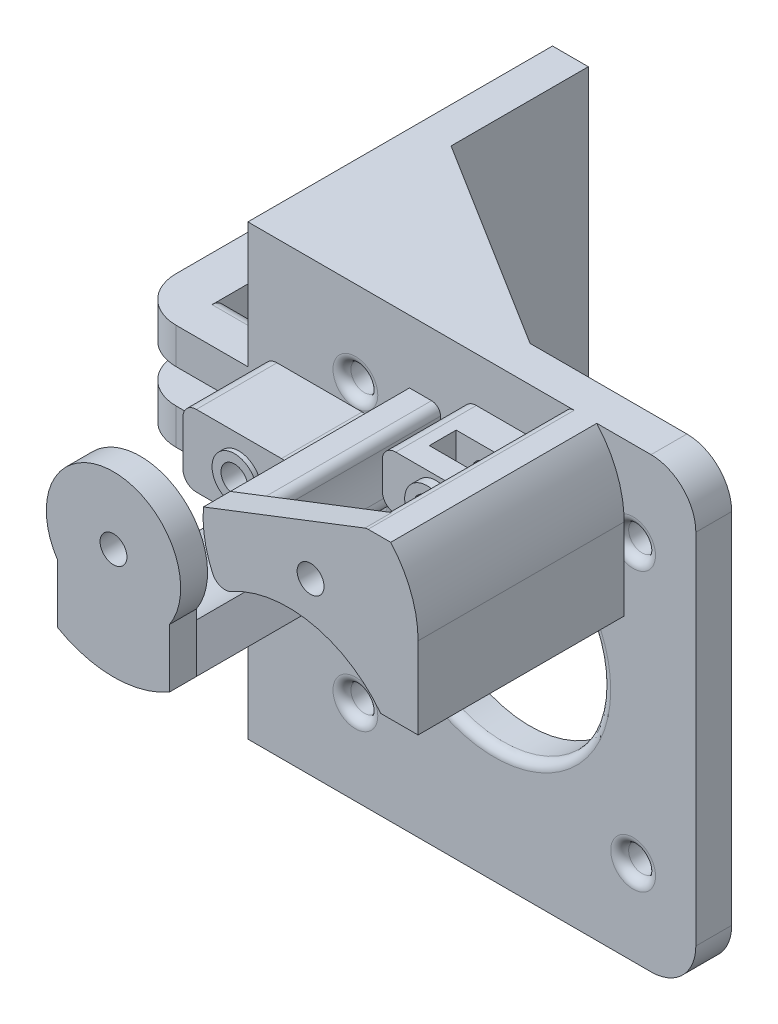
SolidWorks part; units mm, degrees
ref_plane "Plano frontal" through (0, 0, 0) normal (0, 0, 1) x (1, 0, 0)
ref_plane "Plano superior" through (0, 0, 0) normal (0, 1, 0) x (1, 0, 0)
ref_plane "Plano direito" through (0, 0, 0) normal (1, 0, 0) x (0, 0, -1)
sketch "Esboço1" plane through (0, 0, 0) normal (0, 0, 1) x (1, 0, 0)
  line L0 (-22.5, 25) -> (-27.5, 25)
  line L1 (-22.5, 25) -> (22.5, 25)
  line L2 (-22.5, 25) -> (-22.5, -25) construction
  line L3 (-22.5, -25) -> (22.5, -25)
  line L4 (22.5, 25) -> (22.5, -25)
  line L5 (-22.5, 25) -> (22.5, -25) construction
  line L6 (-22.5, -25) -> (22.5, 25) construction
  line L7 (15.5, -15.5) -> (-15.5, -15.5) construction
  line L8 (15.5, -15.5) -> (15.5, 15.5) construction
  line L9 (15.5, 15.5) -> (-15.5, 15.5) construction
  line L10 (-15.5, -15.5) -> (-15.5, 15.5) construction
  line L11 (15.5, -15.5) -> (-15.5, 15.5) construction
  line L12 (15.5, 15.5) -> (-15.5, -15.5) construction
  line L13 (-27.5, 25) -> (-27.5, -25)
  line L14 (-27.5, -25) -> (-22.5, -25)
  circle A0 centre (-15.5, 15.5) radius 1.5
  circle A1 centre (-15.5, -15.5) radius 1.5
  circle A2 centre (15.5, -15.5) radius 1.5
  circle A3 centre (15.5, 15.5) radius 1.5
  circle A4 centre (0, 0) radius 12
  point P0 (0, 0)
  point P6 (0, 0)
  dimension "D2" = 3
  dimension "D5" = 24
  dimension "D1" = 31
  dimension "D3" = 45
  dimension "D4" = 50
  dimension "D6" = 5
extrude "Ressalto-extrusão1" add sketch "Esboço1" along normal blind 4
sketch "Esboço2" plane through (0, 0, 0) normal (0, 0, -1) x (-1, 0, 0)
  line L0 (27.5, 25) -> (27.5, -25) construction
  line L1 (27.5, 25) -> (23.5, 25)
  line L2 (27.5, 25) -> (27.5, -25)
  line L3 (27.5, -25) -> (23.5, -25)
  line L4 (23.5, 25) -> (23.5, -25)
  line L5 (-22.5, 25) -> (27.5, 25) construction
  line L6 (27.5, -25) -> (-22.5, -25) construction
  dimension "D1" = 4
extrude "Ressalto-extrusão2" add sketch "Esboço2" along normal blind 30
sketch "Esboço3" plane through (0, 0, 0) normal (0, 0, -1) x (-1, 0, 0)
  line L0 (0, 0) -> (23.5, 0) construction
  line L1 (23.5, 25) -> (0, 25)
  line L2 (23.5, 25) -> (23.5, 22)
  line L3 (23.5, 22) -> (0, 22)
  line L4 (0, 25) -> (0, 22)
  line L5 (23.5, 25) -> (23.5, -25) construction
  line L6 (0, -25) -> (0, -22)
  line L7 (23.5, -22) -> (0, -22)
  line L8 (23.5, -25) -> (23.5, -22)
  line L9 (23.5, -25) -> (0, -25)
  dimension "D1" = 3
extrude "Ressalto-extrusão3" add sketch "Esboço3" along normal blind 15
chamfer "Chanfro1" distance 15 angle 58 2 edges at (0, -23.5, -15) (0, 23.5, -15) first distance on face at (0, -23.5, -7.5) first distance on face at (0, 23.5, -7.5)
fillet "Filete1" radius 5 2 edges at (22.5, -25, 2) (22.5, 25, 2)
fillet "Filete2" radius 1 5 edges at (12, 0, 4) (-14, -15.5, 4) (17, -15.5, 4) (17, 15.5, 4) (-14, 15.5, 4)
sketch "Esboço4" plane through (-27.5, 0, 0) normal (-1, 0, 0) x (0, 0, 1)
  line L0 (-30, -25) -> (-30, 25) construction
  line L1 (-30, 11) -> (4, 11)
  line L2 (-30, 11) -> (-30, 7)
  line L3 (-30, 7) -> (4, 7)
  line L4 (4, 11) -> (4, 7)
  line L5 (4, 25) -> (4, -25) construction
  line L7 (4, 3.2) -> (-30, 3.2)
  line L8 (4, 3.2) -> (4, -0.8)
  line L9 (4, -0.8) -> (-30, -0.8)
  line L10 (-30, 3.2) -> (-30, -0.8)
  line L11 (4, 25) -> (-30, 25) construction
  dimension "D1" = 3.8
  dimension "D2" = 4
  dimension "D3" = 4
  dimension "D4" = 18
extrude "Ressalto-extrusão4" add sketch "Esboço4" along normal blind 13
sketch "Esboço5" plane through (0, 11, 0) normal (0, 1, 0) x (1, 0, 0)
  line L1 (-31.5, 1.5) -> (-35.5, 1.5)
  line L2 (-31.5, 1.5) -> (-31.5, 4.5)
  line L3 (-31.5, 4.5) -> (-35.5, 4.5)
  line L4 (-35.5, 1.5) -> (-35.5, 4.5)
  line L5 (-27.5, -4) -> (-27.5, 30) construction
  line L6 (-40.5, 13) -> (-27.5, 13) construction
  line L7 (-40.5, -4) -> (-40.5, 30) construction
  line L8 (-27.5, -4) -> (-27.5, 30) construction
  line L9 (-31.5, 1.5) -> (-35.5, 4.5) construction
  line L10 (-33.5, 3) -> (-33.5, 13) construction
  line L11 (-35.5, 24.5) -> (-35.5, 21.5)
  line L12 (-31.5, 21.5) -> (-35.5, 21.5)
  line L13 (-31.5, 24.5) -> (-31.5, 21.5)
  line L14 (-31.5, 24.5) -> (-35.5, 24.5)
  dimension "D1" = 4
  dimension "D2" = 4
  dimension "D3" = 3
  dimension "D4" = 10
extrude "Corte-extrusão1" cut sketch "Esboço5" against normal blind 15
fillet "Filete3" radius 5 4 edges at (-40.5, 1.2, 4) (-40.5, 9, 4) (-40.5, 1.2, -30) (-40.5, 9, -30)
fillet "Filete4" radius 1.5 8 edges at (-33.5, -0.8, -24.5) (-33.5, -0.8, -21.5) (-33.5, -0.8, -4.5) (-33.5, -0.8, -1.5) (-33.5, 11, -24.5) (-33.5, 11, -1.5) (-33.5, 11, -4.5) (-33.5, 11, -21.5)
sketch "Esboço6" plane through (0, 0, 4) normal (0, 0, 1) x (1, 0, 0)
  line L0 (17.5, 25) -> (-27.5, 25) construction
  line L1 (22.5, -20) -> (22.5, 20) construction
  line L2 (11, 17) -> (11, 6.9282)
  line L3 (14.5, 17) -> (14.5, 0)
  line L4 (14.5, 0) -> (13, 0)
  line L6 (5.3723, 25) -> (11.4443, 25)
  line L7 (-9.4611, 17.9657) -> (-5.945, 17.9657)
  arc A0 (14.5, 17) -> (11.4443, 25) centre (2.5, 17) ccw
  arc A1 (11, 17) -> (5.3723, 25) centre (2.5, 17) ccw
  circle A4 centre (0, 0) radius 13 construction
  arc A5 (-4.5099, 12.1926) -> (-7.6118, 10.5385) centre (0, 0) ccw
  arc A8 (13, 0) -> (11, 6.9282) centre (0, 0) ccw
  arc A9 (-9.4611, 17.9657) -> (-7.6118, 10.5385) centre (2.5, 17) ccw
  arc A10 (-5.945, 17.9657) -> (-4.5099, 12.1926) centre (2.5, 17) ccw
  dimension "D1" = 24
  dimension "D2" = 17
  dimension "D3" = 8
  dimension "D4" = 20
extrude "Ressalto-extrusão5" add sketch "Esboço6" along normal blind 20
fillet "Filete5" radius 1 3 edges at (-4.5099, 12.1926, 14) (-5.945, 17.9657, 14) (5.3723, 25, 14)
sketch "Esboço7" plane through (0, 0, 4) normal (0, 0, 1) x (1, 0, 0)
  line L1 (8.5, 14) -> (-3.5, 14)
  line L2 (8.5, 14) -> (8.5, 20)
  line L3 (8.5, 20) -> (-3.5, 20)
  line L4 (-3.5, 14) -> (-3.5, 20)
  line L5 (8.5, 14) -> (-3.5, 20) construction
  line L6 (8.5, 20) -> (-3.5, 14) construction
  circle A0 centre (2.5, 17) radius 3.5 construction
  arc A1 (11, 17) -> (8.2466, 23.2632) centre (2.5, 17) ccw construction
  dimension "D1" = 7
  dimension "D2" = 12
  dimension "D3" = 6
extrude "Ressalto-extrusão6" add sketch "Esboço7" along normal blind 9
sketch "Esboço8" plane through (0, 0, 24) normal (0, 0, 1) x (1, 0, 0)
  line L0 (-9.4611, 17.9657) -> (8.5621, 24.9327)
  line L2 (11.4443, 25) -> (8.9226, 25)
  line L3 (14.5, 0) -> (14.5, 17) construction
  line L4 (14.5, 7.901) -> (14.5, 17)
  line L5 (10.3235, 7.901) -> (14.5, 7.901)
  arc A0 (-9.4611, 17.9657) -> (-7.6118, 10.5385) centre (2.5, 17) ccw
  arc A1 (14.4746, 17.78) -> (11.4443, 25) centre (2.5, 17) ccw construction
  arc A2 (8.9226, 25) -> (8.2466, 23.2632) centre (8.9226, 24) ccw construction
  arc A3 (-5.5304, 11.765) -> (-7.6118, 10.5385) centre (0, 0) ccw construction
  arc A4 (11, 6.9282) -> (-5.5304, 11.765) centre (0, 0) ccw construction
  arc A5 (-5.5304, 11.765) -> (-7.6118, 10.5385) centre (0, 0) ccw
  arc A6 (10.3235, 7.901) -> (-5.5304, 11.765) centre (0, 0) ccw
  arc A7 (8.9226, 25) -> (8.5621, 24.9327) centre (8.9226, 24) ccw
  arc A8 (14.5, 17) -> (11.4443, 25) centre (2.5, 17) ccw construction
  arc A9 (14.5, 17) -> (11.4443, 25) centre (2.5, 17) ccw
extrude "Ressalto-extrusão7" add sketch "Esboço8" along normal blind 3
sketch "Esboço9" plane through (0, 0, 24) normal (0, 0, -1) x (-1, 0, 0)
  circle A0 centre (-2.5, 17) radius 3
  circle A2 centre (-2.5, 17) radius 3.5 construction
  dimension "D1" = 6
extrude "Ressalto-extrusão8" add sketch "Esboço9" along normal blind 1
sketch "Esboço10" plane through (0, 0, 23) normal (0, 0, -1) x (-1, 0, 0)
  circle A0 centre (-2.5, 17) radius 1.5
  circle A2 centre (-2.5, 17) radius 3 construction
  dimension "D1" = 3
extrude "Corte-extrusão2" cut sketch "Esboço10" against normal through all and the other way blind 19
sketch "Esboço11" plane through (0, 25, 0) normal (0, 1, 0) x (1, 0, 0)
  line L0 (2.5, -13) -> (2.5, -10.5) construction
  line L1 (5.75, -10.5) -> (-0.75, -10.5)
  line L2 (5.75, -10.5) -> (5.75, -7.5)
  line L3 (5.75, -7.5) -> (-0.75, -7.5)
  line L4 (-0.75, -10.5) -> (-0.75, -7.5)
  line L5 (1, -13) -> (4, -13) construction
  line L6 (-1, -13) -> (6, -13) construction
  dimension "D1" = 2.5
  dimension "D2" = 6.5
  dimension "D3" = 3
extrude "Corte-extrusão3" cut sketch "Esboço11" against normal through all
fillet "Filete6" radius 1.5 4 edges at (-3.5, 14, 8.5) (8.5, 14, 8.5) (8.5, 20, 8.5) (-3.5, 20, 8.5)
sketch "Esboço12" plane through (0, 0, 13) normal (0, 0, 1) x (1, 0, 0)
  circle A0 centre (2.5, 17) radius 1.5
  circle A1 centre (2.5, 17) radius 2.5
  dimension "D1" = 5
extrude "Ressalto-extrusão9" add sketch "Esboço12" along normal blind 1
sketch "Esboço13" plane through (0, 0, 24) normal (0, 0, 1) x (1, 0, 0)
  line L0 (11, 7.901) -> (14.5, 7.901) construction
  line L1 (7.1918, 7.901) -> (18.6624, 7.901)
  line L2 (7.1918, 7.901) -> (7.1918, -1.4338)
  line L3 (7.1918, -1.4338) -> (18.6624, -1.4338)
  line L4 (18.6624, 7.901) -> (18.6624, -1.4338)
extrude "Corte-extrusão4" cut sketch "Esboço13" against normal up to surface (20 mm away) up to face at (-13, -15.5, 4)
sketch "Esboço14" plane through (0, 0, 4) normal (0, 0, 1) x (1, 0, 0)
  line L0 (-19.5, 9) -> (-25.75, -1.8253) construction
  line L1 (-19.5, 9) -> (-19.5, -3.5) construction
  line L2 (-19.5, 9) -> (-13.25, -1.8253) construction
  line L3 (-25.75, -1.8253) -> (-23.75, 1.6388)
  line L4 (-13.25, -1.8253) -> (-15.25, 1.6388)
  line L5 (-27.5, 25) -> (-27.5, 11) construction
  line L6 (-13.25, 13) -> (-25.75, 13)
  line L7 (-13.25, 13) -> (-13.25, 5)
  line L8 (-13.25, 5) -> (-25.75, 5)
  line L9 (-25.75, 13) -> (-25.75, 5)
  line L10 (-13.25, 13) -> (-25.75, 5) construction
  line L11 (-13.25, 5) -> (-25.75, 13) construction
  line L12 (8.9226, 25) -> (-27.5, 25) construction
  arc A0 (-23.75, 1.6388) -> (-15.25, 1.6388) centre (-19.5, 9) ccw
  arc A1 (-25.75, -1.8253) -> (-13.25, -1.8253) centre (-19.5, 9) ccw
  point P10 (0, 0)
  dimension "D1" = 17
  dimension "D2" = 25
  dimension "D3" = 30
  dimension "D4" = 30
  dimension "D5" = 12.5
  dimension "D6" = 8
  dimension "D7" = 16
  dimension "D8" = 8
extrude "Ressalto-extrusão10" add sketch "Esboço14" along normal up to surface (23 mm away) up to face at (1, 17, 27)
sketch "Esboço15" plane through (0, 0, 27) normal (0, 0, 1) x (1, 0, 0)
  line L1 (-25.75, 13) -> (-13.25, 13)
  line L2 (-25.75, 13) -> (-25.75, 5)
  line L3 (-25.75, 5) -> (-13.25, 5)
  line L4 (-13.25, 13) -> (-13.25, 5)
extrude "Corte-extrusão5" cut sketch "Esboço15" against normal up to surface (14 mm away) up to face at (2.5, 17, 13)
sketch "Esboço16" plane through (0, 0, 27) normal (0, 0, 1) x (1, 0, 0)
  line L0 (-25.75, 13) -> (-13.25, 4.7084) construction
  line L1 (-25.75, -1.8253) -> (-25.75, 4.7084)
  line L2 (-13.25, -1.8253) -> (-13.25, 4.7084)
  arc A0 (-13.25, 4.7084) -> (-25.75, 4.7084) centre (-19.5, 8.8542) ccw
  arc A4 (-25.75, -1.8253) -> (-13.25, -1.8253) centre (-19.5, 9) ccw construction
  arc A5 (-25.75, -1.8253) -> (-13.25, -1.8253) centre (-19.5, 9) ccw
  point P5 (0, 0)
  point P13 (0, 0)
  dimension "D1" = 15
extrude "Ressalto-extrusão11" add sketch "Esboço16" against normal blind 3
sketch "Esboço17" plane through (0, 0, 27) normal (0, 0, 1) x (1, 0, 0)
  circle A0 centre (-19.5, 8.8542) radius 1.5
  arc A1 (-13.25, 4.7084) -> (-25.75, 4.7084) centre (-19.5, 8.8542) ccw construction
  dimension "D1" = 3
extrude "Corte-extrusão6" cut sketch "Esboço17" against normal up to surface (23 mm away) up to face at (-5.7572, 8.1204, 4)
fillet "Filete7" radius 1.5 4 edges at (-13.25, 5, 8.5) (-25.75, 5, 8.5) (-13.25, 13, 8.5) (-25.75, 13, 8.5)
sketch "Esboço18" plane through (0, 0, 13) normal (0, 0, 1) x (1, 0, 0)
  circle A0 centre (-19.5, 8.8542) radius 1.5
  circle A1 centre (-19.5, 8.8542) radius 2.5
  dimension "D1" = 5
extrude "Ressalto-extrusão12" add sketch "Esboço18" along normal blind 0.5
sketch "Esboço19" plane through (0, 0, 24) normal (0, 0, -1) x (-1, 0, 0)
  circle A0 centre (19.5, 8.8542) radius 1.5
  circle A1 centre (19.5, 8.8542) radius 2.5
  dimension "D1" = 5
extrude "Ressalto-extrusão13" add sketch "Esboço19" along normal blind 0.5
fillet "Filete8" radius 1.5 1 edges at (-7.6118, 10.5385, 15.5)
